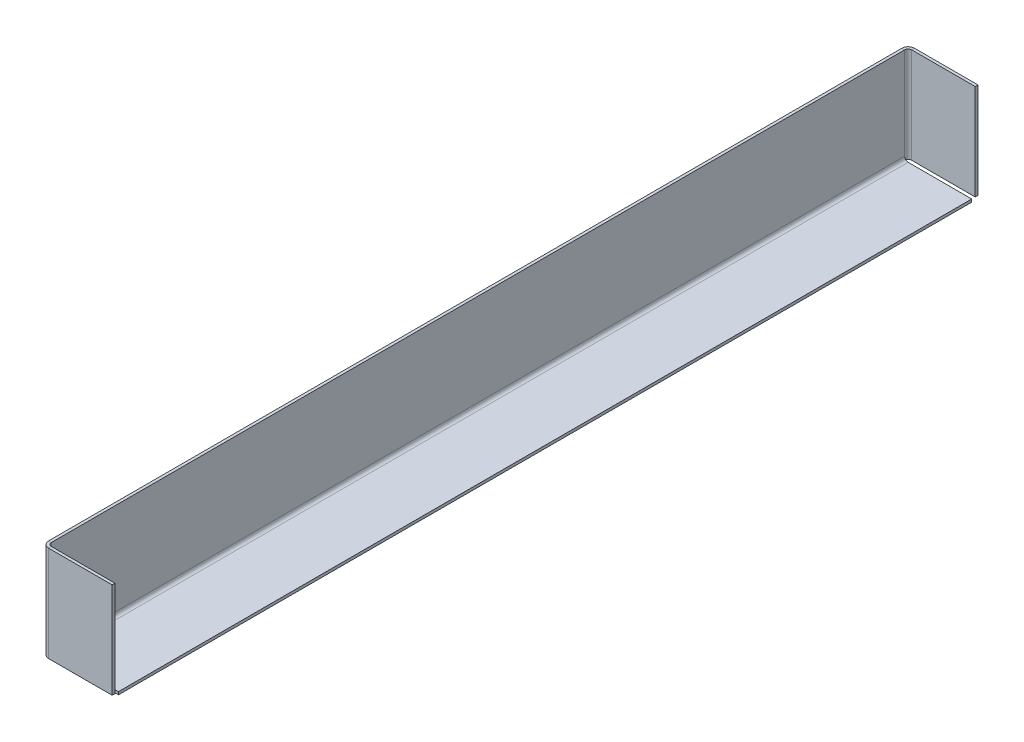
SolidWorks part; units mm, degrees
note: The reader was unsure of these and kept them because the rebuilt part matched: flange length of "Edge-Flange1", "Edge-Flange2", "Edge-Flange3".
ref_plane "Front Plane" through (0, 0, 0) normal (0, 0, 1) x (1, 0, 0)
ref_plane "Top Plane" through (0, 0, 0) normal (0, 1, 0) x (1, 0, 0)
ref_plane "Right Plane" through (0, 0, 0) normal (1, 0, 0) x (0, 0, -1)
sketch "Sketch2" plane through (0, 0, 0) normal (1, 0, 0) x (0, 0, -1)
  line L1 (123.2, 13.7) -> (-123.2, 13.7)
  line L2 (123.2, 13.7) -> (123.2, -13.7)
  line L3 (123.2, -13.7) -> (-123.2, -13.7)
  line L4 (-123.2, 13.7) -> (-123.2, -13.7)
  line L5 (123.2, 13.7) -> (-123.2, -13.7) construction
  line L6 (123.2, -13.7) -> (-123.2, 13.7) construction
  point P0 (0, 0)
  dimension "D1" = 246.4
  dimension "D2" = 27.4
base flange "Base-Flange2" sketch "Sketch2" thickness 0.8 reverse thickness direction yes parameters "D1"=0.7366
edge flange "Edge-Flange1" sketch "Sketch20" flange angle 90 flange length 19.2 flange position material outside bend radius 1 thickness 0.8 relief rectangular parameters "D6"=10
sketch "Sketch20" plane through (0.8, 0, 123.2) normal (0, 0, 1) x (0, -1, 0)
  line L2 (-13.7, 0) -> (-13.7, 19.2)
  line L3 (-13.7, 19.2) -> (13.7, 19.2)
  line L4 (13.7, 19.2) -> (13.7, 0)
  line L7 (-13.7, 0) -> (13.7, 0) construction
  line L8 (-13.7, 0) -> (13.7, 0)
bend "EdgeBend1" bend radius 1 bend angle 90 parameters "D5"=1
edge flange "Edge-Flange2" sketch "Sketch23" flange angle 90 flange length 19.2 flange position material outside bend radius 1 thickness 0.8 relief rectangular parameters "D6"=10
sketch "Sketch23" plane through (0.8, 0, -123.2) normal (0, 0, -1) x (0, 1, 0)
  line L0 (-13.7, 0) -> (13.7, 0) construction
  line L1 (-13.7, 0) -> (13.7, 0)
  line L2 (-13.7, 0) -> (-13.7, 19.2)
  line L3 (-13.7, 19.2) -> (13.7, 19.2)
  line L4 (13.7, 19.2) -> (13.7, 0)
bend "EdgeBend2" bend radius 1 bend angle 90 parameters "D5"=2
edge flange "Edge-Flange3" sketch "Sketch26" flange angle 90 flange length 19.2 flange position material outside bend radius 1 thickness 0.8 relief none parameters "D6"=10
sketch "Sketch26" plane through (0.8, -13.7, 0) normal (0, -1, 0) x (0, 0, -1)
  line L2 (-122.2, 0) -> (-122.2, 19.2)
  line L3 (-122.2, 19.2) -> (122.2, 19.2)
  line L4 (122.2, 19.2) -> (122.2, 0)
  line L7 (-122.2, 0) -> (122.2, 0) construction
  line L8 (-122.2, 0) -> (122.2, 0)
bend "EdgeBend3" bend radius 1 bend angle 90 parameters "D5"=3
sketch "Bend-Lines4" [suppressed] plane through (0, 0, 0) normal (0, 1, 0) x (1, 0, 0)
sketch "Bounding-Box4" [suppressed] plane through (0, 0, 0) normal (0, 1, 0) x (1, 0, 0)
sheet metal parameters "Sheet-Metal3" thickness 0.8 parameters "D1"=0.7366
flat pattern "Flat-Pattern3" [suppressed]
sketch "Bend-Lines5" plane through (0, 0, 0) normal (0, 1, 0) x (1, 0, 0)
sketch3d "Bounding-Box5" [suppressed]
  line L0 (123.2, -13.7, 0) -> (-123.2, -13.7, 0) construction
  line L1 (123.2, 13.7, 0) -> (-123.2, 13.7, 0) construction
  line L2 (123.2, -13.7, 0) -> (123.2, 13.7, 0) construction
  line L3 (-123.2, -13.7, 0) -> (-123.2, 13.7, 0) construction
sheet metal parameters "Sheet-Metal4" thickness 0.8 parameters "D1"=0.7366
flat pattern "Flat-Pattern3"
sketch "Bend-Lines5" plane through (0, 0, 0) normal (-1, 0, 0) x (0, 0, 1)
  line L0 (123.2996, -13.7) -> (123.2996, 13.7) construction
  line L1 (123.2996, -13.7) -> (123.2996, 13.7) construction
sketch3d "Bounding-Box5" [suppressed]
  line L0 (-123.2, -13.7, 0) -> (142.5991, -13.7, 0) construction
  line L1 (-123.2, 13.7, 0) -> (142.5991, 13.7, 0) construction
  line L2 (-123.2, -13.7, 0) -> (-123.2, 13.7, 0) construction
  line L3 (142.5991, -13.7, 0) -> (142.5991, 13.7, 0) construction
bend of the flat pattern "Flatten-<EdgeBend1>1"
sheet metal parameters "Sheet-Metal5" thickness 0.8 parameters "D1"=0.7366
flat pattern "Flat-Pattern3"
sketch "Bend-Lines5" plane through (0, 0, 0) normal (-1, 0, 0) x (0, 0, 1)
  line L0 (123.2996, -13.7) -> (123.2996, 13.7) construction
  line L1 (123.2996, -13.7) -> (123.2996, 13.7) construction
  line L2 (-123.2996, 13.7) -> (-123.2996, -13.7) construction
  line L3 (-123.2996, 13.7) -> (-123.2996, -13.7) construction
sketch3d "Bounding-Box5" [suppressed]
  line L0 (-142.5991, -13.7, 0) -> (142.5991, -13.7, 0) construction
  line L1 (-142.5991, 13.7, 0) -> (142.5991, 13.7, 0) construction
  line L2 (-142.5991, -13.7, 0) -> (-142.5991, 13.7, 0) construction
  line L3 (142.5991, -13.7, 0) -> (142.5991, 13.7, 0) construction
bend of the flat pattern "Flatten-<EdgeBend1>1"
bend of the flat pattern "Flatten-<EdgeBend2>1"
sheet metal parameters "Sheet-Metal6" thickness 0.8 parameters "D1"=0.7366
flat pattern "Flat-Pattern3"
sketch "Bend-Lines5" plane through (0, 0, 0) normal (-1, 0, 0) x (0, 0, 1)
  line L0 (123.2996, -13.7) -> (123.2996, 13.7) construction
  line L1 (123.2996, -13.7) -> (123.2996, 13.7) construction
  line L2 (-123.2996, 13.7) -> (-123.2996, -13.7) construction
  line L3 (-123.2996, 13.7) -> (-123.2996, -13.7) construction
  line L4 (-122.2, -13.7996) -> (122.2, -13.7996) construction
  line L5 (-122.2, -13.7996) -> (122.2, -13.7996) construction
sketch3d "Bounding-Box5" [suppressed]
  line L0 (-142.5991, -33.0991, 0) -> (142.5991, -33.0991, 0) construction
  line L1 (-142.5991, 13.7, 0) -> (142.5991, 13.7, 0) construction
  line L2 (-142.5991, -33.0991, 0) -> (-142.5991, 13.7, 0) construction
  line L3 (142.5991, -33.0991, 0) -> (142.5991, 13.7, 0) construction
bend of the flat pattern "Flatten-<EdgeBend1>1"
bend of the flat pattern "Flatten-<EdgeBend2>1"
bend of the flat pattern "Flatten-<EdgeBend3>1"
